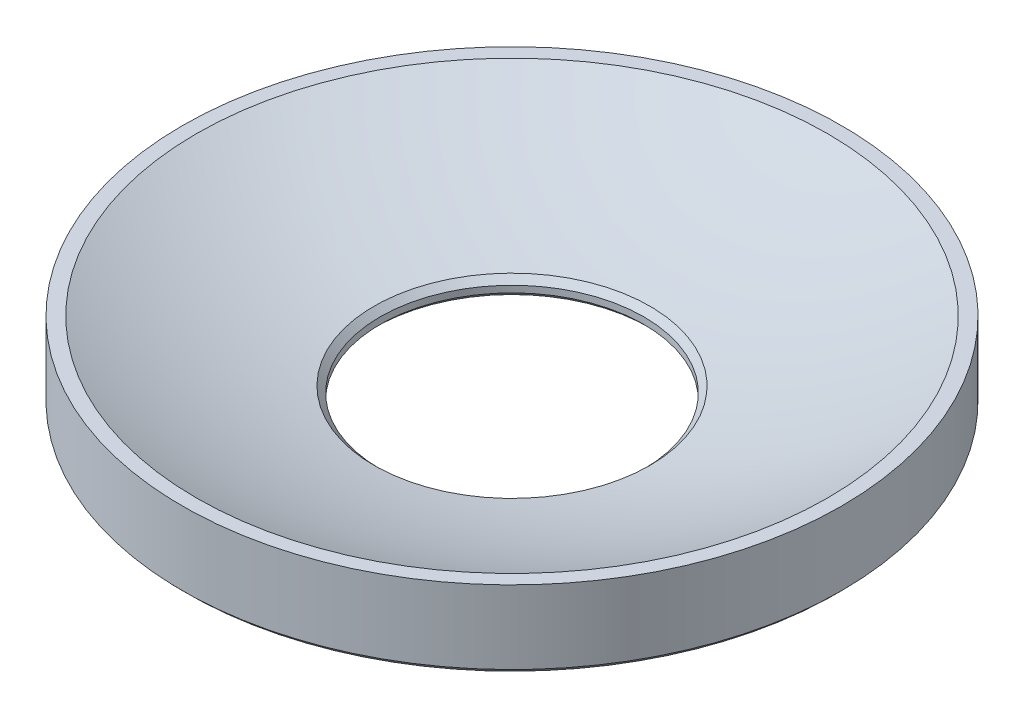
SolidWorks part; units mm, degrees
material "2.0321 (CuZn37)"
ref_plane "Płaszczyzna przednia" through (0, 0, 0) normal (0, 0, 1) x (1, 0, 0)
ref_plane "Płaszczyzna górna" through (0, 0, 0) normal (0, 1, 0) x (1, 0, 0)
ref_plane "Płaszczyzna prawa" through (0, 0, 0) normal (1, 0, 0) x (0, 0, -1)
sketch "Szkic1" plane through (0, 0, 0) normal (0, 0, 1) x (1, 0, 0)
  line L0 (0, 0.2493) -> (0, 22.0709) construction
  line L1 (8, 0) -> (20, 0)
  line L2 (20, 0) -> (20, 4.7493)
  line L3 (20, 4.7493) -> (19.1507, 4.7493)
  line L5 (0, 0.2493) -> (-8.397, 0.2493) construction
  line L6 (8, 1) -> (8, 0)
  arc A0 (8, 1) -> (19.1507, 4.7493) centre (0, 43.2493) ccw
  arc A1 (8, 1) -> (0, 0.2493) centre (0, 43.2493) cw construction
  dimension "D5" = 16
  dimension "D1" = 4.5
  dimension "D2" = 1
  dimension "D3" = 43
  dimension "D4" = 40
  dimension "D6" = 4.7493
  dimension "D7" = 3.7493
revolve "Obrót1" add sketch "Szkic1" angle 360 about L0
chamfer "Sfazowanie1" distance 0.3 angle 45 3 edges at (8, 1, 0) (8, 0, 0) (20, 0, 0) first distance on face at (8, 0, 0) first distance on face at (20, 0, 0) first distance on face at (20, 4.7493, 0)
